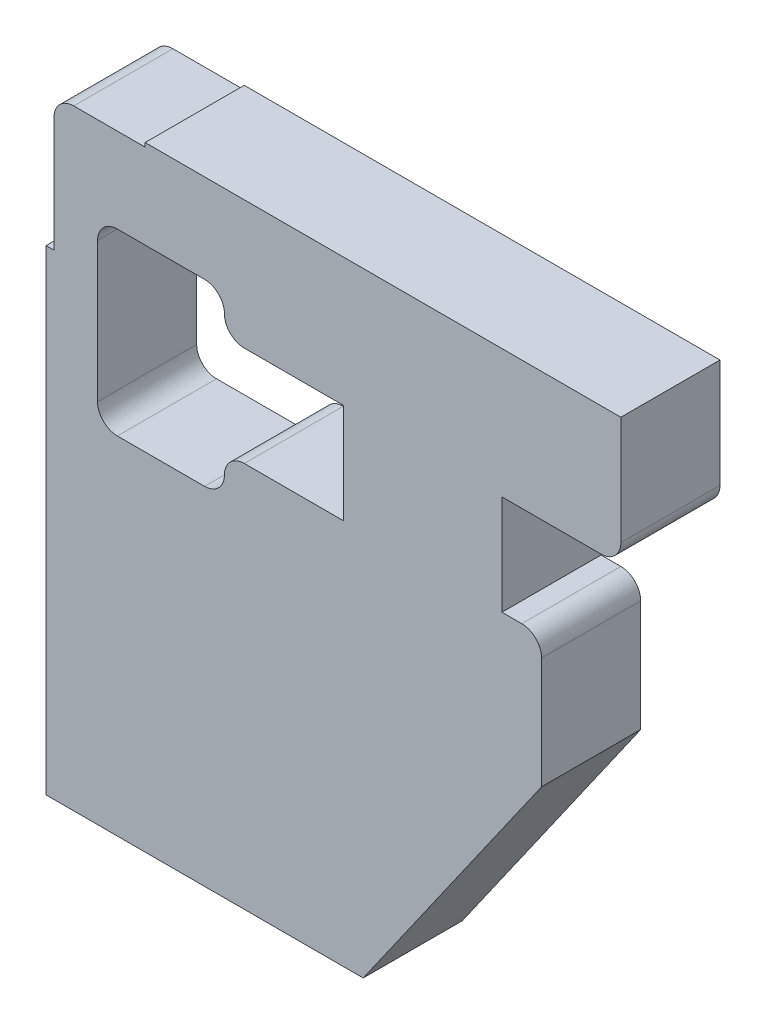
SolidWorks part; units mm, degrees
material "PBT General Purpose"
ref_plane "Front Plane" through (0, 0, 0) normal (0, 0, 1) x (1, 0, 0)
ref_plane "Top Plane" through (0, 0, 0) normal (0, 1, 0) x (1, 0, 0)
ref_plane "Right Plane" through (0, 0, 0) normal (1, 0, 0) x (0, 0, -1)
sketch "frame_outline" plane through (0, 0, 0) normal (0, 0, 1) x (1, 0, 0)
  line L0 (0, 0) -> (0, -0.4) construction
  line L1 (0, 0) -> (0.3, 0) construction
  line L2 (0, -0.4) -> (0.05, -0.4) construction
  line L3 (0.3, 0) -> (0.3, -0.05) construction
  line L8 (0.3, -0.05) -> (1.5, -0.05)
  line L19 (0.3, -0.05) -> (0.3, -0.06)
  line L20 (0.3, -0.06) -> (0.07, -0.06)
  line L21 (0.07, -0.06) -> (0.07, -0.4)
  line L62 (0.05, -0.4) -> (0.07, -0.4)
  line L63 (0.05, -0.4) -> (0.05, -1.6)
  line L64 (0.05, -1.6) -> (0.85, -1.6)
  line L65 (0.85, -1.6) -> (1.3, -0.9573)
  line L66 (1.3, -0.9573) -> (1.3, -0.626)
  line L67 (1.3, -0.626) -> (1.2, -0.626)
  line L68 (1.2, -0.626) -> (1.2, -0.374)
  line L69 (1.2, -0.374) -> (1.5, -0.374)
  line L70 (1.5, -0.374) -> (1.5, -0.05)
  line L71 (0, -0.5) -> (1.8135, -0.5) construction
  line L72 (0.5, -0.374) -> (0.8, -0.374)
  line L73 (0.8, -0.374) -> (0.8, -0.626)
  line L74 (0.8, -0.626) -> (0.5, -0.626)
  line L75 (0.5, -0.626) -> (0.5, -0.726)
  line L76 (0.5, -0.726) -> (0.18, -0.726)
  line L77 (0.18, -0.726) -> (0.18, -0.274)
  line L78 (0.18, -0.274) -> (0.5, -0.274)
  line L79 (0.5, -0.274) -> (0.5, -0.374)
  line L80 (1.2, -0.05) -> (1.2, -1.1001) construction
  line L81 (0.8, -0.374) -> (1.2, -0.374) construction
  point P22 (1.2, -0.5)
  point P32 (1, -0.374)
  point P33 (1.3, -0.7917)
  dimension "D2" = 0.3
  dimension "D6" = 1.2
  dimension "D4" = 0.05
  dimension "D1" = 0.05
  dimension "D3" = 0.4
  dimension "D5" = 0.02
  dimension "D7" = 0.01
  dimension "D8" = 1.2
  dimension "D9" = 0.5
  dimension "D10" = 0.252
  dimension "D11" = 0.1
  dimension "D12" = 0.32
  dimension "D13" = 0.3
  dimension "D15" = 0.4
  dimension "D16" = 0.85
  dimension "D18" = 1
  dimension "D17" = 55
  dimension "D14" = 0.3
  dimension "D19" = 0.1
  dimension "D20" = 1.0501
extrude "Boss-Extrude1" add sketch "frame_outline" along normal mid plane 0.25
fillet "Fillet1" radius 0.05 9 edges at (1.3, -0.626, 0) (1.5, -0.374, 0) (0.5, -0.374, 0) (0.5, -0.626, 0) (0.5, -0.726, 0) (0.18, -0.726, 0) (0.5, -0.274, 0) (0.18, -0.274, 0) (0.07, -0.06, 0)
equation "\"t\"= 0.25'thickness of the sheets"
equation "\"t_cf\" = 0.115'thickness of single carbon fiber layer"
equation "\"t_kapton\" = 0.025'thickness of single Kapton flex layer"
equation "\"t_fr4\" = 0.1'thickness of FR4 with copper layer"
equation "\"joint_flex\"= 0.1'Width of flextures gap"
equation "\"joint_flex_eff\"= 0.02'Width of flecture after castelation"
equation "\"joint_fold\"= 0.2'Width of folding joints for 90deg fold"
equation "\"gap_tolerance\"= 0.002'Width to have interfecence fit between carbon fiber inserts"
equation "\"assemble_angle\"= 90'Angle of assembly parts"
equation "\"D1@Boss-Extrude1\"=\"t\""
equation "\"D4@frame_outline\"=\"joint_flex\"/2"
equation "\"D1@frame_outline\"=\"joint_flex\"/2"
equation "\"D10@frame_outline\"=\"t\"+\"gap_tolerance\""
equation "\"D9@frame_outline\"=\"link_lift\""
equation "\"link_lift\"= 0.5'Actuation linkage amplification for the lift motion"
equation "\"link_swing\"= 0.45'Actuation linkage amplification for the swing motion"
